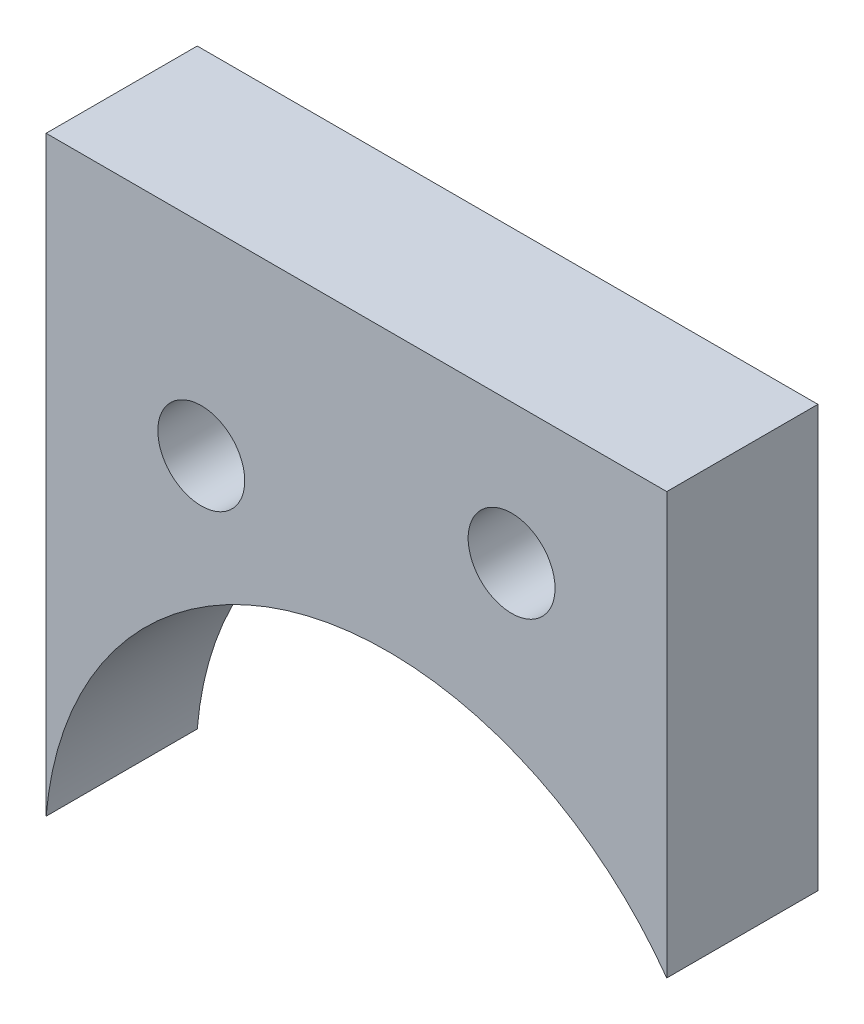
SolidWorks part; units mm, degrees
ref_plane "Front Plane" through (0, 0, 0) normal (0, 0, 1) x (1, 0, 0)
ref_plane "Top Plane" through (0, 0, 0) normal (0, 1, 0) x (1, 0, 0)
ref_plane "Right Plane" through (0, 0, 0) normal (1, 0, 0) x (0, 0, -1)
sketch "Sketch1" plane through (0, 0, 0) normal (0, 0, 1) x (1, 0, 0)
  line L2 (0, 0.9394) -> (0, 20)
  line L3 (0, 20) -> (20, 20)
  line L4 (20, 6.4251) -> (20, 20)
  circle A0 centre (5, 13.5) radius 1.4
  circle A1 centre (15, 15.5) radius 1.4
  arc A2 (20, 6.4251) -> (0, 0.9394) centre (11.01, 0) ccw
extrude "Boss-Extrude1" add sketch "Sketch1" along normal blind 4.87
